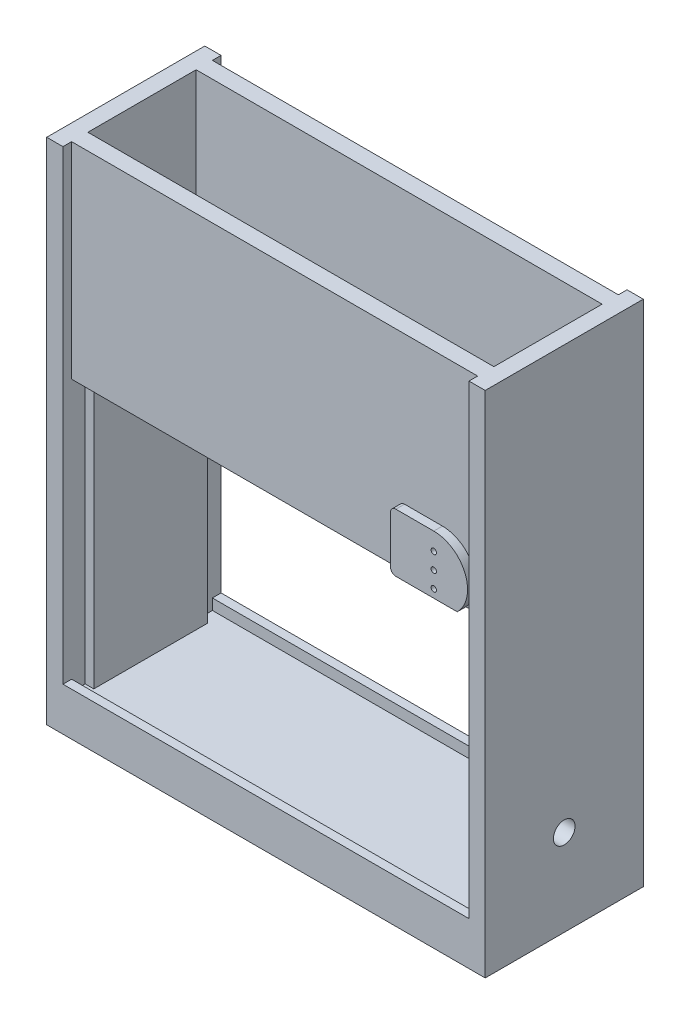
SolidWorks part; units mm, degrees
ref_plane "Front Plane" through (0, 0, 0) normal (0, 0, 1) x (1, 0, 0)
ref_plane "Top Plane" through (0, 0, 0) normal (0, 1, 0) x (1, 0, 0)
ref_plane "Right Plane" through (0, 0, 0) normal (1, 0, 0) x (0, 0, -1)
sketch "Sketch1" plane through (0, 0, 0) normal (0, 1, 0) x (1, 0, 0)
  line L1 (-75, -21) -> (75, -21)
  line L2 (-75, -21) -> (-75, 21)
  line L3 (-75, 21) -> (75, 21)
  line L4 (75, -21) -> (75, 21)
  line L5 (-75, -21) -> (75, 21) construction
  line L6 (-75, 21) -> (75, -21) construction
  point P0 (0, 0)
  dimension "D1" = 42
  dimension "D2" = 150
extrude "Boss-Extrude1" add sketch "Sketch1" along normal blind 3.2
sketch "Sketch2" plane through (0, 0, 0) normal (0, -1, 0) x (1, 0, 0)
  line L0 (75, 21) -> (75, -21) construction
  line L1 (-81, 26) -> (81, 26)
  line L2 (-81, 26) -> (-81, -26)
  line L3 (-81, -26) -> (81, -26)
  line L4 (81, 26) -> (81, -26)
  line L5 (-81, 26) -> (81, -26) construction
  line L6 (-81, -26) -> (81, 26) construction
  line L7 (75, -21) -> (-75, -21) construction
  point P0 (0, 0)
  dimension "D1" = 6
  dimension "D2" = 5
extrude "Boss-Extrude2" add sketch "Sketch2" along normal blind 6
sketch "Sketch4" plane through (0, 0, -21) normal (0, 0, -1) x (-1, 0, 0)
  line L1 (-75, 0) -> (75, 0)
  line L2 (-75, 0) -> (-75, 100)
  line L3 (-75, 100) -> (75, 100)
  line L4 (75, 0) -> (75, 100)
  line L5 (-75, 100) -> (75, 100)
  line L6 (-75, 100) -> (-75, 106)
  line L7 (-75, 106) -> (75, 106)
  line L8 (75, 100) -> (75, 106)
  line L9 (-75, 106) -> (75, 106)
  line L10 (-75, 106) -> (-75, 176)
  line L11 (-75, 176) -> (75, 176)
  line L12 (75, 106) -> (75, 176)
  point P5 (73.6966, 106)
  dimension "D1" = 100
  dimension "D2" = 6
  dimension "D3" = 70
sketch "Sketch3" plane through (0, 0, 0) normal (0, 1, 0) x (1, 0, 0)
  line L0 (-81, 26) -> (81, 26) construction
  line L1 (81, -26) -> (75, -26)
  line L2 (81, -26) -> (81, 26)
  line L3 (81, 26) -> (75, 26)
  line L4 (75, -26) -> (75, 26)
  line L5 (75, -21) -> (75, 21) construction
  line L6 (-81, -26) -> (-75, -26)
  line L7 (-81, -26) -> (-81, 26)
  line L8 (-81, 26) -> (-75, 26)
  line L9 (-75, -26) -> (-75, 26)
  line L10 (-75, 21) -> (-75, -21) construction
extrude "Boss-Extrude3" add sketch "Sketch3" along normal up to vertex (176 mm away) up to point (75, 176, -21)
sketch "Sketch5" plane through (75, 0, 0) normal (-1, 0, 0) x (0, 0, 1)
  line L0 (-26, 176) -> (-26, 0) construction
  line L1 (-26, 100) -> (26, 100)
  line L2 (-26, 100) -> (-26, 106)
  line L3 (-26, 106) -> (26, 106)
  line L4 (26, 100) -> (26, 106)
  line L5 (26, 176) -> (26, 0) construction
extrude "Boss-Extrude4" add sketch "Sketch5" along normal up to next
extrude "Boss-Extrude5" add sketch "Sketch1<2>" against normal blind 3.2 from surface starting at face at (0, 100, 0)
sketch "Sketch1<2>" plane through (0, 0, 0) normal (0, 1, 0) x (1, 0, 0) same geometry as "Sketch1"
sketch "Sketch6" plane through (0, 106, 0) normal (0, 1, 0) x (1, 0, 0)
  line L0 (-75, -26) -> (-75, 26) construction
  line L1 (75, -26) -> (-75, -26)
  line L2 (75, -26) -> (75, -20)
  line L3 (75, -20) -> (-75, -20)
  line L4 (-75, -26) -> (-75, -20)
  line L5 (75, -26) -> (75, 26) construction
  line L6 (-75, 26) -> (75, 26)
  line L7 (-75, 26) -> (-75, 20)
  line L8 (-75, 20) -> (75, 20)
  line L9 (75, 26) -> (75, 20)
  dimension "D1" = 6
extrude "Boss-Extrude6" add sketch "Sketch6" along normal up to surface (70 mm away) up to face at (78, 176, 0)
sketch "Sketch7" plane through (0, 106, 0) normal (0, 1, 0) x (1, 0, 0)
  line L0 (75, 0) -> (-75, 0) construction
  line L1 (75, -10) -> (75, -20) construction
  line L2 (-75, 10) -> (75, 10) construction
  line L3 (-75, 10) -> (-75, -10) construction
  line L4 (75, 20) -> (-75, 20)
  line L5 (-75, 20) -> (-75, -20)
  line L6 (-75, -20) -> (75, -20)
  line L7 (75, -20) -> (75, 20)
  line L8 (75, 20) -> (-75, 20) construction
  line L9 (-75, 20) -> (-75, -20) construction
  line L10 (-75, -20) -> (75, -20) construction
  line L11 (75, -20) -> (75, 20) construction
  line L12 (-75, -10) -> (75, -10) construction
  line L13 (75, 10) -> (75, -10) construction
  line L14 (-75, 10) -> (75, -10) construction
  line L15 (-75, -10) -> (75, 10) construction
  line L16 (75, -20) -> (65, -20) construction
  line L17 (65, -20) -> (65, -10) construction
  line L18 (65, -20) -> (75, -10) construction
  line L19 (70, -18) -> (70, -20) construction
  line L21 (65, -20) -> (59, -20)
  line L22 (65, -20) -> (65, 20)
  line L23 (65, 20) -> (59, 20)
  line L24 (59, -20) -> (59, 20)
  line L25 (75, -20) -> (65, -20)
  line L26 (75, -20) -> (75, 20)
  line L27 (75, 20) -> (65, 20)
  line L28 (65, -20) -> (65, 20)
  circle A0 centre (70, -15) radius 3
  circle A1 centre (70, 15) radius 3
  point P6 (0, 0)
  line M16 (75, 20) -> (-75, 20)
  line M18 (-75, -20) -> (75, -20)
  line M19 (75, -20) -> (75, 20)
  dimension "D2" = 20
  dimension "D3" = 2
  dimension "D4" = 6
  dimension "D1" = 0
extrude "Cut-Extrude1" cut sketch "Sketch7" against normal up to next contours L22 A0 A1 M18 M19 M16 | A0 | A1 region at (70, 106, 0) region at (70, 106, 15) region at (70, 106, -15)
extrude "Boss-Extrude7" add sketch "Sketch7<3>" along normal offset from surface (54 mm away) 16 contours L24 L22 M18 M16 region at (62, 106, 0) up to face at (0, 176, 0)
sketch "Sketch7<3>" plane through (0, 106, 0) normal (0, 1, 0) x (1, 0, 0) same geometry as "Sketch7"
sketch "Sketch8" plane through (0, 0, -26) normal (0, 0, -1) x (-1, 0, 0)
  line L0 (81, -6) -> (81, 176) construction
  line L1 (-81, -6) -> (81, -6)
  line L2 (-81, -6) -> (-81, 4)
  line L3 (-81, 4) -> (81, 4)
  line L4 (81, -6) -> (81, 4)
  dimension "D1" = 10
extrude "Boss-Extrude8" add sketch "Sketch8" along normal blind 3.2
mirror "Mirror1" about plane through (0, 0, 0) normal (0, 0, 1) of "Boss-Extrude8"
sketch "Sketch9" plane through (0, 3.2, 0) normal (0, 1, 0) x (1, 0, 0)
  line L4 (75, -21) -> (75, 21)
  line L5 (75, 21) -> (-75, 21)
  line L6 (-75, 21) -> (-75, -21)
  line L7 (-75, -21) -> (75, -21)
  line L8 (75, -21) -> (75, 21)
  line L9 (75, 21) -> (-75, 21)
  line L10 (-75, 21) -> (-75, -21)
  line L11 (-75, -21) -> (75, -21)
  dimension "D1" = 0
extrude "Cut-Extrude2" cut sketch "Sketch9" against normal up to surface (3.2 mm away) up to face at (0, 0, -23.5)
sketch "Sketch10" plane through (0, 96.8, 0) normal (0, -1, 0) x (1, 0, 0)
  line L4 (-75, -21) -> (75, -21)
  line L5 (75, -21) -> (75, -20)
  line L6 (75, 21) -> (-75, 21)
  line L7 (-75, 21) -> (-75, -21)
  line L8 (-75, -21) -> (75, -21)
  line L9 (75, -21) -> (75, -20)
  line L10 (75, 21) -> (-75, 21)
  line L11 (-75, 21) -> (-75, -21)
  line L16 (65, 20) -> (75, 20)
  line L17 (65, 20) -> (75, 20)
  line L18 (75, 20) -> (75, 21)
  line L19 (75, 20) -> (75, 21)
  line L20 (75, -20) -> (65, -20)
  line L21 (75, -20) -> (65, -20)
  line L22 (65, -20) -> (65, 20)
  line L23 (65, -20) -> (65, 20)
  dimension "D1" = 0
extrude "Cut-Extrude3" cut sketch "Sketch10" against normal up to surface (3.2 mm away) up to face at (0, 100, -23.5)
sketch "Sketch11" plane through (75, 0, 0) normal (-1, 0, 0) x (0, 0, 1)
  line L0 (-26, 0) -> (26, 0) construction
  line L1 (-21, 93.5) -> (21, 93.5)
  line L2 (-21, 93.5) -> (-21, 0)
  line L3 (-21, 0) -> (21, 0)
  line L4 (21, 93.5) -> (21, 0)
  line L6 (-26, 100) -> (-20, 100) construction
  line L7 (0, 93.5) -> (0, 100) construction
  line L8 (10, 93.5) -> (10, 100)
  line L9 (10, 100) -> (21, 100)
  line L10 (21, 100) -> (21, 93.5)
  point P5 (0, 0)
  point P13 (0, 0)
  line M8 (26, 100) -> (20, 100)
  line M11 (-26, 0) -> (26, 0)
  dimension "D1" = 42
  dimension "D2" = 6.5
  dimension "D3" = 10
extrude "Boss-Extrude9" add sketch "Sketch11" along normal blind 3.2 contours L4 L1 L2 M11 | L10 L8 L1 M8 region at (75, 46.75, 0) region at (75, 96.75, 15.5)
mirror "Mirror2" about plane through (0, 0, 0) normal (1, 0, 0) of "Boss-Extrude9"
sketch "Sketch12" plane through (0, 100, 0) normal (0, 1, 0) x (1, 0, 0)
  line L4 (71.8, -10) -> (71.8, -20)
  line L5 (71.8, -20) -> (75, -20)
  line L6 (75, -20) -> (75, -10)
  line L7 (75, -10) -> (71.8, -10)
  line L8 (71.8, -10) -> (71.8, -20)
  line L9 (71.8, -20) -> (75, -20)
  line L10 (75, -20) -> (75, -10)
  line L11 (75, -10) -> (71.8, -10)
  dimension "D1" = 0
extrude "Boss-Extrude10" add sketch "Sketch12" along normal blind 6
sketch "Sketch13" plane through (71.8, 0, 0) normal (-1, 0, 0) x (0, 0, 1)
  line L0 (0, 20) -> (0, 0) construction
  line L1 (-21, 0) -> (21, 0) construction
  circle A0 centre (0, 20) radius 4
  point P2 (0, 0)
  dimension "D1" = 8
  dimension "D2" = 20
extrude "Cut-Extrude4" cut sketch "Sketch13" against normal up to next contours A0
sketch "Sketch14" plane through (0, 0, -20) normal (0, 0, 1) x (1, 0, 0)
  line L8 (65, 100) -> (59, 106) construction
  line L9 (59, 106) -> (65, 112) construction
  line L10 (65, 112) -> (59, 118) construction
  line L16 (65, 160) -> (65, 100)
  line L17 (65, 100) -> (75, 100)
  line L18 (75, 100) -> (75, 176)
  line L19 (75, 176) -> (-75, 176)
  line L20 (-75, 176) -> (-75, 106)
  line L21 (-75, 106) -> (59, 106)
  line L22 (59, 106) -> (59, 160)
  line L23 (59, 160) -> (65, 160)
  line L24 (65, 160) -> (65, 100) construction
  line L25 (65, 100) -> (75, 100) construction
  line L26 (75, 100) -> (75, 176) construction
  line L27 (75, 176) -> (-75, 176) construction
  line L28 (-75, 176) -> (-75, 106) construction
  line L29 (-75, 106) -> (59, 106) construction
  line L30 (59, 106) -> (59, 160) construction
  line L31 (59, 160) -> (65, 160) construction
  circle A0 centre (62, 103) radius 1
  circle A1 centre (62, 109) radius 1
  circle A2 centre (62, 115) radius 1
  dimension "D2" = 2
  dimension "D1" = 0
extrude "Cut-Extrude5" cut sketch "Sketch14" against normal up to next
sketch "Sketch15" plane through (0, 0, -26) normal (0, 0, -1) x (-1, 0, 0)
  line L0 (-70.6747, 100) -> (-53.3253, 100)
  line L1 (75, 100) -> (-75, 100) construction
  line L2 (-62, 96.5) -> (-62, 100) construction
  line L3 (-53.3253, 100) -> (-46, 100)
  line L4 (-46, 100) -> (-46, 121.5)
  line L5 (-46, 121.5) -> (-62, 121.5)
  arc A0 (-70.6747, 100) -> (-53.3253, 100) centre (-62, 109) cw
  arc A1 (-53.3253, 100) -> (-70.6747, 100) centre (-62, 109) cw construction
  point P1 (-62, 121.5)
  circle M4 centre (-62, 103) radius 1
  circle M5 centre (-62, 109) radius 1
  circle M6 centre (-62, 115) radius 1
  line M13 (-75, 100) -> (75, 100)
  dimension "D1" = 3.5
  dimension "D2" = 3.5
  dimension "D3" = 16
sketch "Sketch16" plane through (0, 0, -26) normal (0, 0, -1) x (-1, 0, 0)
  line L1 (75, 4) -> (81, 4)
  line L2 (75, 4) -> (75, 176)
  line L3 (75, 176) -> (81, 176)
  line L4 (81, 4) -> (81, 176)
  line L5 (-81, 176) -> (-75, 176)
  line L6 (-81, 176) -> (-81, 4)
  line L7 (-81, 4) -> (-75, 4)
  line L8 (75, 4) -> (81, 4)
  line L9 (81, 4) -> (81, 176)
  line L10 (81, 176) -> (-81, 176)
  line L11 (-81, 176) -> (-81, 4)
  line L12 (-81, 4) -> (-75, 4)
  line L13 (-75, 4) -> (-75, 100)
  line L14 (-75, 100) -> (75, 100)
  line L15 (75, 100) -> (75, 4)
  line L16 (75, 4) -> (81, 4) construction
  line L17 (81, 4) -> (81, 176) construction
  line L18 (81, 176) -> (-81, 176) construction
  line L19 (-81, 176) -> (-81, 4) construction
  line L20 (-81, 4) -> (-75, 4) construction
  line L21 (-75, 4) -> (-75, 100) construction
  line L22 (-75, 100) -> (75, 100) construction
  line L23 (75, 100) -> (75, 4) construction
  line L24 (-75, 176) -> (-75, 4)
  dimension "D1" = 0
extrude "Boss-Extrude11" add sketch "Sketch16" along normal blind 3.2
mirror "Mirror3" about plane through (0, 0, 0) normal (0, 0, 1) of "Boss-Extrude11"
sketch "Sketch17" plane through (0, -6, 0) normal (0, -1, 0) x (1, 0, 0)
  line L0 (-81, 29.2) -> (-81, -29.2) construction
  line L1 (75, -26) -> (-75, -26)
  line L2 (75, -26) -> (75, 26)
  line L3 (75, 26) -> (-75, 26)
  line L4 (-75, -26) -> (-75, 26)
  line L5 (75, -26) -> (-75, 26) construction
  line L6 (75, 26) -> (-75, -26) construction
  line L7 (81, -29.2) -> (-81, -29.2) construction
  point P0 (0, 0)
  line M3 (81, -29.2) -> (81, 29.2)
  line M4 (81, 29.2) -> (-81, 29.2)
  line M5 (-81, 29.2) -> (-81, -29.2)
  line M6 (-81, -29.2) -> (81, -29.2)
  dimension "D1" = 6
  dimension "D2" = 3.2
extrude "Boss-Extrude12" add sketch "Sketch17" along normal blind 6 contours L1 L4 L3 L2 M6 M3 M4 M5 region at (0, -6, -27.478)
extrude "Boss-Extrude14" add sketch "Sketch15" along normal blind 3.2 contours L5 A0 L4 M13 | A0 M13 M5 M6 M4 region at (73.2862, 113.5537, -26) region at (49.2804, 112.2182, -26)
fillet "Fillet1" radius 2 2 edges at (46, 100, -27.6) (46, 121.5, -27.6)
mirror "Mirror4" about plane through (0, 0, 0) normal (0, 0, 1) of "Fillet1", "Boss-Extrude14"
equation "\"glass_width\" = 150"
equation "\"glass_height\"= 100"
equation "\"glass_thickness\"= 4"
equation "\"brood_space\"= 42"
equation "\"t1\"= 6"
equation "\"t2\"= 3.2"
equation "\"D2@Sketch2\"=1+ \"glass_thickness\""
equation "\"foodchamber_height\"= 70"
equation "\"D2@Sketch11\"=\"t1\"+0.5"
